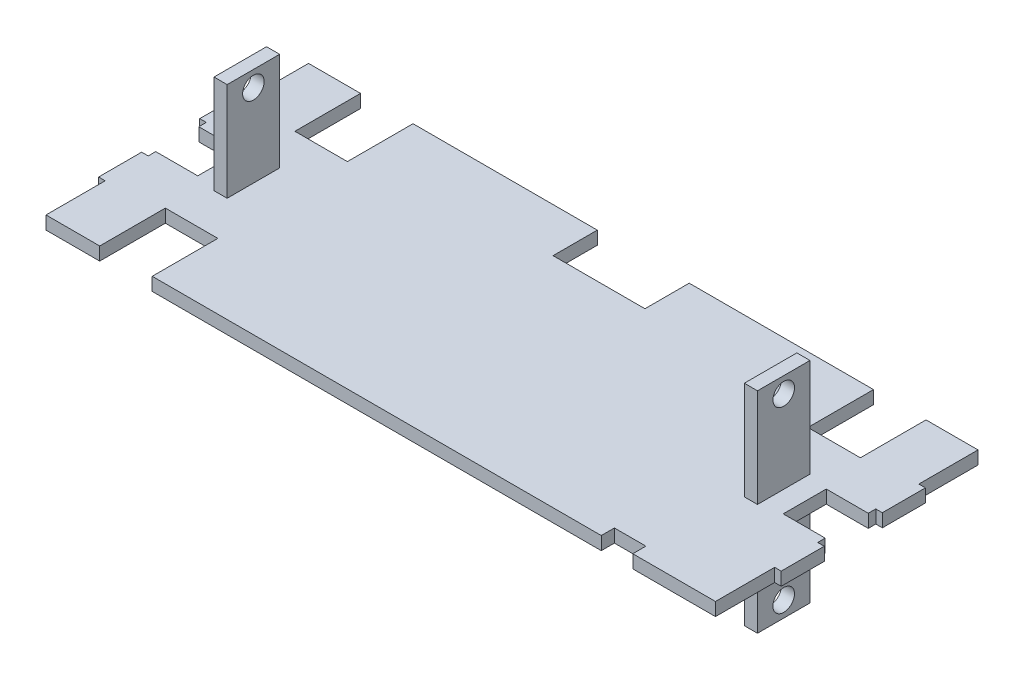
SolidWorks part; units mm, degrees
ref_plane "Front Plane" through (0, 0, 0) normal (0, 0, 1) x (1, 0, 0)
ref_plane "Top Plane" through (0, 0, 0) normal (0, 1, 0) x (1, 0, 0)
ref_plane "Right Plane" through (0, 0, 0) normal (1, 0, 0) x (0, 0, -1)
sketch "Sketch1" plane through (0, 0, 0) normal (0, 1, 0) x (1, 0, 0)
  line L1 (161.925, -63.5) -> (121.92, -63.5)
  line L2 (161.925, -63.5) -> (161.925, -34.8747)
  line L3 (161.925, 63.5) -> (136.779, 63.5)
  line L4 (-161.925, -63.5) -> (-161.925, -34.8747)
  line L5 (161.925, -63.5) -> (-161.925, 63.5) construction
  line L6 (161.925, 63.5) -> (-161.925, -63.5) construction
  line L7 (161.925, 10.414) -> (141.605, 10.414)
  line L9 (161.925, -10.414) -> (141.605, -10.414)
  line L10 (141.605, 10.414) -> (141.605, -10.414)
  line L11 (-136.779, 63.5) -> (-161.925, 63.5)
  line L13 (-161.925, -10.414) -> (-141.605, -10.414)
  line L14 (-141.605, 10.414) -> (-141.605, -10.414)
  line L15 (-161.925, 10.414) -> (-141.605, 10.414)
  line L17 (-141.605, 0) -> (127, 0) construction
  line L18 (-161.925, 14.0467) -> (-165.1, 14.0467)
  line L20 (-161.925, 34.8747) -> (-165.1, 34.8747)
  line L21 (-165.1, 14.0467) -> (-165.1, 34.8747)
  line L22 (-161.925, -34.8747) -> (-165.1, -34.8747)
  line L23 (-165.1, -14.0467) -> (-165.1, -34.8747)
  line L24 (-161.925, -14.0467) -> (-165.1, -14.0467)
  line L27 (161.925, -14.0467) -> (165.1, -14.0467)
  line L28 (165.1, -14.0467) -> (165.1, -34.8747)
  line L29 (161.925, -34.8747) -> (165.1, -34.8747)
  line L30 (161.925, 34.8747) -> (165.1, 34.8747)
  line L31 (165.1, 14.0467) -> (165.1, 34.8747)
  line L32 (161.925, 14.0467) -> (165.1, 14.0467)
  line L34 (-161.925, 34.8747) -> (-161.925, 63.5)
  line L35 (-161.925, -14.0467) -> (-161.925, -10.414)
  line L36 (161.925, 34.8747) -> (161.925, 63.5)
  line L37 (161.925, -14.0467) -> (161.925, -10.414)
  line L38 (-161.925, 10.414) -> (-161.925, 14.0467)
  line L39 (161.925, 10.414) -> (161.925, 14.0467)
  line L40 (-136.779, 63.5) -> (-136.779, 31.75)
  line L41 (-136.779, 31.75) -> (-111.379, 31.75)
  line L42 (-111.379, 63.5) -> (-111.379, 31.75)
  line L44 (111.379, 63.5) -> (111.379, 31.75)
  line L45 (111.379, 31.75) -> (136.779, 31.75)
  line L46 (136.779, 63.5) -> (136.779, 31.75)
  line L47 (111.379, 63.5) -> (22.2286, 63.5)
  line L48 (106.68, -63.5) -> (-106.68, -63.5)
  line L50 (106.68, -63.5) -> (106.68, -57.15)
  line L51 (106.68, -57.15) -> (121.92, -57.15)
  line L52 (121.92, -63.5) -> (121.92, -57.15)
  line L56 (-135.9408, -63.5) -> (-161.925, -63.5)
  line L57 (-106.68, -63.5) -> (-110.5408, -63.5)
  line L59 (-135.9408, -63.5) -> (-135.9408, -31.75)
  line L60 (-135.9408, -31.75) -> (-110.5408, -31.75)
  line L61 (-110.5408, -63.5) -> (-110.5408, -31.75)
  line L62 (-22.2286, 63.5) -> (-111.379, 63.5)
  line L64 (22.2286, 63.5) -> (22.2286, 42.0861)
  line L65 (22.2286, 42.0861) -> (-22.2286, 42.0861)
  line L66 (-22.2286, 63.5) -> (-22.2286, 42.0861)
  line L69 (0, 42.0861) -> (0, -72.39) construction
  point P0 (0, 0)
  point P6 (141.605, 0)
  point P47 (121.92, -60.325)
  point P48 (124.079, 31.75)
  point P49 (-124.079, 31.75)
  point P50 (0, 63.5)
  point P52 (-123.2408, -31.75)
  dimension "D1" = 323.85
  dimension "D2" = 127
  dimension "D3" = 20.828
  dimension "D5" = 3.175
  dimension "D6" = 20.828
  dimension "D4" = 20.32
  dimension "D7" = 31.75
  dimension "D8" = 25.4
  dimension "D9" = 25.4
  dimension "D10" = 31.75
  dimension "D13" = 15.24
  dimension "D14" = 6.35
  dimension "D15" = 40.005
  dimension "D16" = 25.4
  dimension "D17" = 31.75
  dimension "D18" = 41.8592
  dimension "D11" = 41.021
  dimension "D12" = 41.021
extrude "Boss-Extrude1" add sketch "Sketch1" along normal mid plane 6.35
sketch "Sketch2" plane through (0, 0, 0) normal (0, 1, 0) x (1, 0, 0)
  line L0 (-141.605, 10.414) -> (-141.605, -10.414) construction
  line L1 (125.095, -12.7) -> (131.445, -12.7)
  line L2 (125.095, -12.7) -> (125.095, 12.7)
  line L3 (125.095, 12.7) -> (131.445, 12.7)
  line L4 (131.445, -12.7) -> (131.445, 12.7)
  line L5 (125.095, -12.7) -> (131.445, 12.7) construction
  line L6 (125.095, 12.7) -> (131.445, -12.7) construction
  line L9 (-125.095, -12.7) -> (-125.095, 12.7)
  line L10 (-125.095, 12.7) -> (-131.445, 12.7)
  line L11 (-131.445, -12.7) -> (-131.445, 12.7)
  line L12 (-125.095, -12.7) -> (-131.445, -12.7)
  line L13 (141.605, -10.414) -> (141.605, 10.414) construction
  point P0 (128.27, 0)
  point P10 (141.605, 0)
  dimension "D1" = 10.16
  dimension "D2" = 10.16
  dimension "D3" = 25.4
  dimension "D4" = 25.4
  dimension "D5" = 6.35
  dimension "D6" = 6.35
  dimension "D7" = 6.35
extrude "Boss-Extrude2" add sketch "Sketch2" along normal mid plane 101.6
sketch "Sketch3" plane through (-131.445, 0, 0) normal (-1, 0, 0) x (0, 0, 1)
  line L0 (-12.7, 50.8) -> (12.7, 50.8) construction
  line L1 (-12.7, -50.8) -> (12.7, -50.8) construction
  circle A0 centre (0, 43.18) radius 5.207
  circle A1 centre (0, -43.18) radius 5.207
  point P4 (0, 50.8)
  dimension "D1" = 10.414
  dimension "D2" = 10.414
  dimension "D3" = 7.62
  dimension "D4" = 7.62
  dimension "D5" = 86.36
extrude "Cut-Extrude1" cut sketch "Sketch3" against normal through all both and the other way through all
equation "\"length\"= 12.75"
equation "\"width\"=5"
equation "\"height\"= 0.25"
equation "\"D1@Sketch1\"=\"length\""
equation "\"D2@Sketch1\"=\"width\""
equation "\"eyebolt width\"= 0.82"
equation "\"eyebolt length\"= 0.8"
equation "\"D3@Sketch1\"=\"eyebolt width\""
equation "\"D4@Sketch1\"=\"eyebolt length\""
equation "\"lead screw holder height\"= 2.76"
equation "\"lead screw diameter\"=0.41"
equation "\"D1@Sketch3\"=\"lead screw diameter\""
equation "\"distance from holders to board\"=0.4"
equation "\"D2@Sketch3\"=\"lead screw diameter\""
equation "\"lead_screw_dist\"=3.4"
equation "\"D5@Sketch3\"=\"lead_screw_dist\""
